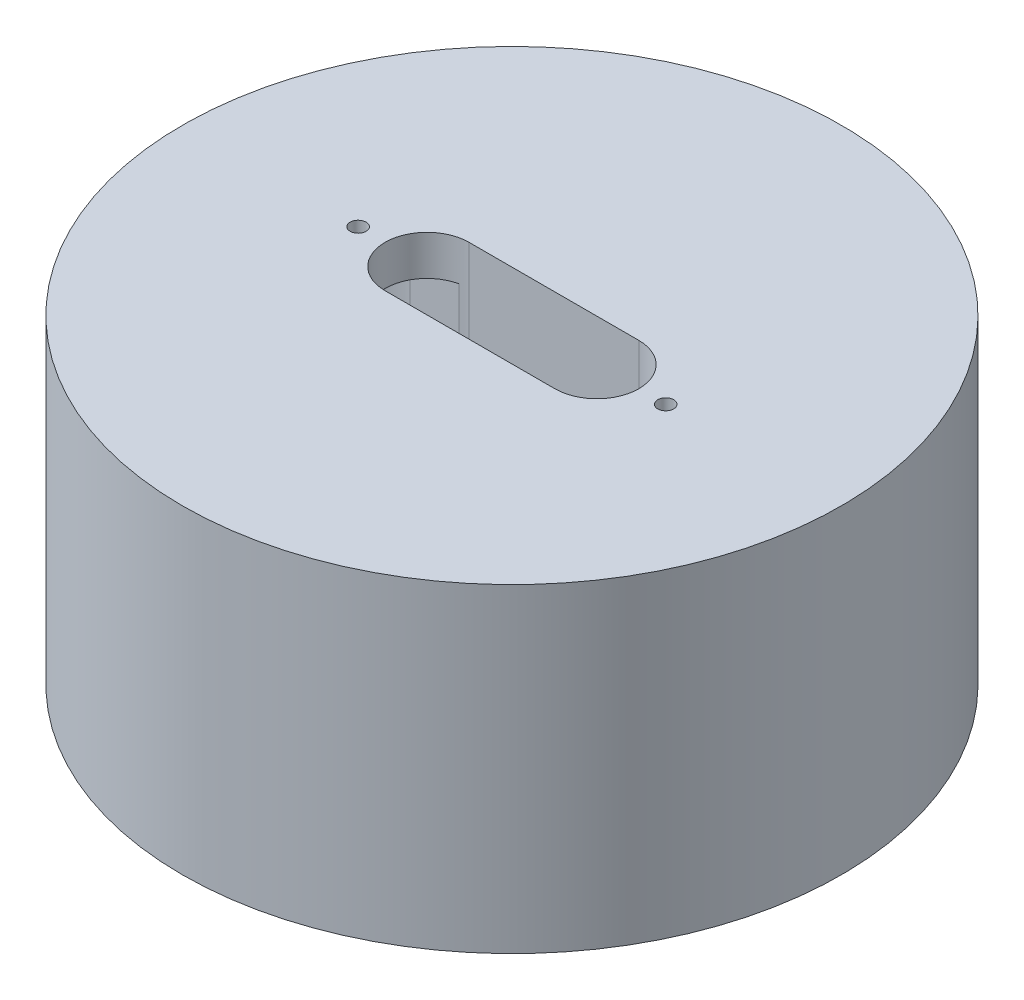
SolidWorks part; units mm, degrees
ref_plane "前视基准面" through (0, 0, 0) normal (0, 0, 1) x (1, 0, 0)
ref_plane "上视基准面" through (0, 0, 0) normal (0, 1, 0) x (1, 0, 0)
ref_plane "右视基准面" through (0, 0, 0) normal (1, 0, 0) x (0, 0, -1)
other "Configuration Table"
sketch "草图1" plane through (0, 0, 0) normal (0, 1, 0) x (1, 0, 0)
  circle A0 centre (0, 0) radius 16.5
  dimension "D1" = 33
extrude "凸台-拉伸1" add sketch "草图1" along normal blind 16
sketch "草图2" plane through (0, 0, 0) normal (0, -1, 0) x (-1, 0, 0)
  circle A0 centre (0, 0) radius 14.25
  dimension "D1" = 28.5
extrude "切除-拉伸1" cut sketch "草图2" against normal blind 5.1
sketch "草图3" plane through (0, 5.1, 0) normal (0, -1, 0) x (1, 0, 0)
  circle A0 centre (0, 0) radius 9.5
  dimension "D1" = 19
extrude "切除-拉伸2" cut sketch "草图3" against normal blind 5
sketch "草图4" plane through (0, 0, 0) normal (0, -1, 0) x (1, 0, 0)
  line L1 (4.25, 2.1) -> (-4.25, 2.1)
  line L2 (4.25, 2.1) -> (4.25, -2.1)
  line L3 (4.25, -2.1) -> (-4.25, -2.1)
  line L4 (-4.25, 2.1) -> (-4.25, -2.1)
  line L5 (4.25, 2.1) -> (-4.25, -2.1) construction
  line L6 (4.25, -2.1) -> (-4.25, 2.1) construction
  circle A0 centre (-4.25, 0) radius 2.1
  circle A1 centre (4.25, 0) radius 2.1
  dimension "D1" = 4.2
  dimension "D2" = 8.5
extrude "切除-拉伸3" cut sketch "草图4" against normal through all contours L4 A0 | A1 L1 A0 L3 | L2 A1 | L2 A1 | L4 A0 region at (0, 0, 0) region at (5.1413, 0, 0) region at (3.3587, 0, 0) region at (-3.3587, 0, 0) region at (-5.1413, 0, 0)
sketch "草图5" plane through (0, 0, 0) normal (0, -1, 0) x (1, 0, 0)
  line L1 (7.15, 2.05) -> (-7.15, 2.05)
  line L2 (7.15, 2.05) -> (7.15, -2.05)
  line L3 (7.15, -2.05) -> (-7.15, -2.05)
  line L4 (-7.15, 2.05) -> (-7.15, -2.05)
  line L5 (7.15, 2.05) -> (-7.15, -2.05) construction
  line L6 (7.15, -2.05) -> (-7.15, 2.05) construction
  circle A0 centre (-7.15, 0) radius 2.05
  circle A1 centre (7.15, 0) radius 2.05
  dimension "D1" = 4.1
  dimension "D2" = 14.3
extrude "切除-拉伸4" cut sketch "草图5" against normal offset from surface (14 mm away) 2 contours L4 A0 | L2 A1 | L1 L4 L3 L2 region at (8.02, 0, 0) region at (-8.02, 0, 0) up to face at (0, 16, 0)
sketch "草图6" plane through (0, 14, 0) normal (0, -1, 0) x (1, 0, 0)
  circle A0 centre (7.7, 0) radius 0.4
  circle A1 centre (-7.7, 0) radius 0.4
  dimension "D1" = 0.8
extrude "切除-拉伸5" cut sketch "草图6" against normal blind 2
sketch "草图7" plane through (0, 0, 0) normal (0, -1, 0) x (1, 0, 0)
  line L0 (16.5, 0) -> (15, 0) construction
  line L1 (15, 0) -> (0, 0) construction
  circle A0 centre (15, 0) radius 0.4
  circle A1 centre (0, 0) radius 16.5 construction
  dimension "D1" = 0.8
  dimension "D2" = 1.5
extrude "切除-拉伸6" cut sketch "草图7" against normal blind 3
pattern_circular "阵列(圆周)1" count 4 over 360 about axis through (0, 16, 0) along (0, -1, 0) of "切除-拉伸6" reverse direction yes
sketch "草图8" plane through (0, 0, 0) normal (0, -1, 0) x (1, 0, 0)
  line L0 (0, 0) -> (-13.2069, 7.625)
  line L1 (0, 0) -> (-7.625, 13.2069)
  line L2 (0, 0) -> (0, 15.25) construction
  line L3 (0, 0) -> (-15.25, 0) construction
  circle A0 centre (0, 0) radius 15.25
  circle A1 centre (0, 0) radius 14.25 construction
  circle M10 centre (0, 0) radius 14.25
  dimension "D1" = 1
  dimension "D2" = 30
  dimension "D3" = 30
extrude "切除-拉伸7" cut sketch "草图8" against normal up to surface (10.1 mm away) contours L0 L1 M10 | L1 A0 L0 M10 region at (-6.641, 0, 6.641) region at (-10.315, 0, 10.315) up to face at (0, 10.1, 0)
